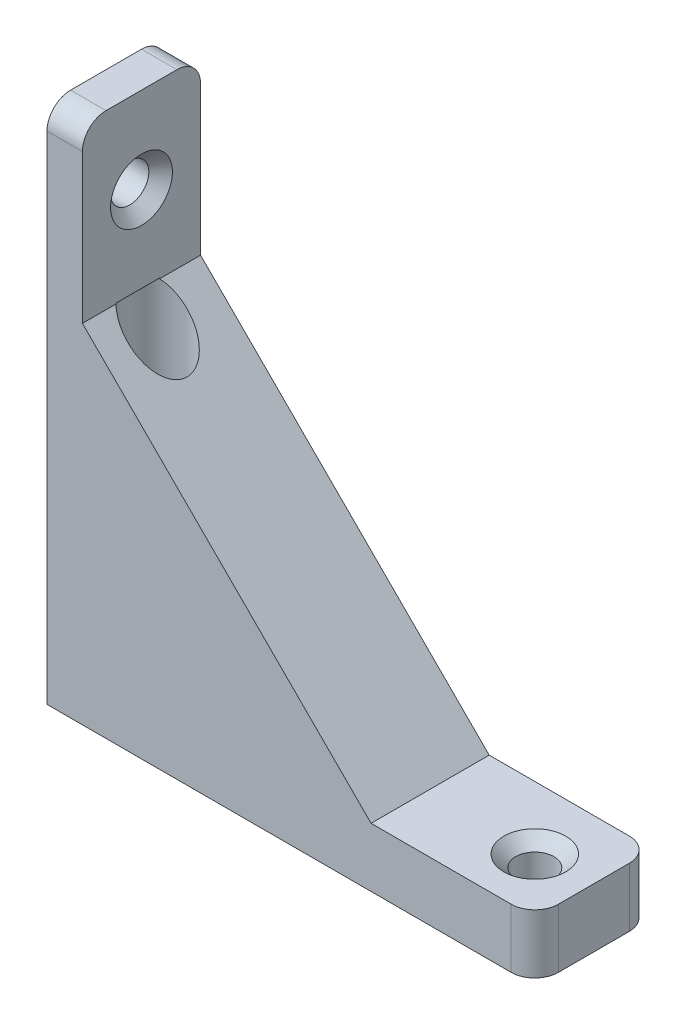
SolidWorks part; units mm, degrees
ref_plane "Piano frontale" through (0, 0, 0) normal (0, 0, 1) x (1, 0, 0)
ref_plane "Piano superiore" through (0, 0, 0) normal (0, 1, 0) x (1, 0, 0)
ref_plane "Piano destro" through (0, 0, 0) normal (1, 0, 0) x (0, 0, -1)
sketch "Schizzo2" plane through (0, 0, 0) normal (0, 0, 1) x (1, 0, 0)
  line L0 (3, 29.4386) -> (27.4386, 5)
  line L1 (0, 0) -> (41.3, 0)
  line L2 (0, 0) -> (0, 5)
  line L3 (27.4386, 5) -> (41.3, 5)
  line L4 (41.3, 0) -> (41.3, 5)
  line L5 (27.4386, 5) -> (3, 5) construction
  line L6 (0, 5) -> (0, 44.0391)
  line L7 (0, 44.0391) -> (3, 44.0391)
  line L8 (3, 29.4386) -> (3, 44.0391)
  line L9 (3, 5) -> (3, 29.4386) construction
  point P5 (41.3, 2.5)
  dimension "D1" = 5
  dimension "D2" = 41.3
  dimension "D3" = 3
  dimension "D4" = 45
extrude "Estrusione-Estrusione1" add sketch "Schizzo2" along normal blind 10 contours L0 L3 L4 L1 L2 L6 L7 L8
sketch "Schizzo3" plane through (0, 5, 0) normal (0, 1, 0) x (1, 0, 0)
  line L0 (36.62, -10) -> (36.62, 5.744) construction
  line L1 (27.4386, -10) -> (41.3, -10) construction
  line L2 (41.3, -10) -> (41.3, 0) construction
  circle A0 centre (36.62, -5.32) radius 1.62
  circle A1 centre (36.62, -5.32) radius 2.5
  dimension "D1" = 3.24
  dimension "D4" = 5
  dimension "D2" = 4.68
  dimension "D3" = 4.68
extrude "Taglio-Estrusione1" cut sketch "Schizzo3" against normal blind 8 contours A0
ref_plane "Piano1" through (0, 5, 0) normal (0, 1, 0) x (1, 0, 0)
sketch "Schizzo5" plane through (0, 5, 0) normal (0, 1, 0) x (1, 0, 0)
  line L0 (0, -10) -> (0, 0) construction
  line L1 (3, -10) -> (27.4386, -10) construction
  circle A0 centre (4.68, -5.32) radius 1.62
  circle A1 centre (4.68, -5.32) radius 2.5
  dimension "D1" = 3.24
  dimension "D4" = 5
  dimension "D2" = 4.68
  dimension "D3" = 4.68
extrude "Taglio-Estrusione4" cut sketch "Schizzo5" against normal blind 24.5 contours A0
extrude "Taglio-Estrusione5" cut sketch "Schizzo5<4>" along normal blind 24.5 contours A1
sketch "Schizzo5<4>" plane through (0, 5, 0) normal (0, 1, 0) x (1, 0, 0) same geometry as "Schizzo5"
chamfer "Smusso4" distance 1 angle 45 1 edges at (4.68, 5, 6.94)
chamfer "Smusso5" distance 1 angle 45 1 edges at (35, 5, 5.32)
sketch "Schizzo6" plane through (3, 0, 0) normal (1, 0, 0) x (0, 0, -1)
  line L0 (0, 44.0391) -> (-10, 29.4386) construction
  circle A0 centre (-5, 36.7389) radius 2.5
  circle A1 centre (-5, 36.7389) radius 1.62
  dimension "D1" = 5
  dimension "D2" = 3.24
extrude "Taglio-Estrusione6" cut sketch "Schizzo6" against normal blind 24.5 contours A1
chamfer "Smusso6" distance 1 angle 45 1 edges at (3, 36.7389, 3.38)
fillet "Raccordo1" radius 2 4 edges at (41.3, 2.5, 10) (41.3, 2.5, 0) (1.5, 44.0391, 0) (1.5, 44.0391, 10)
